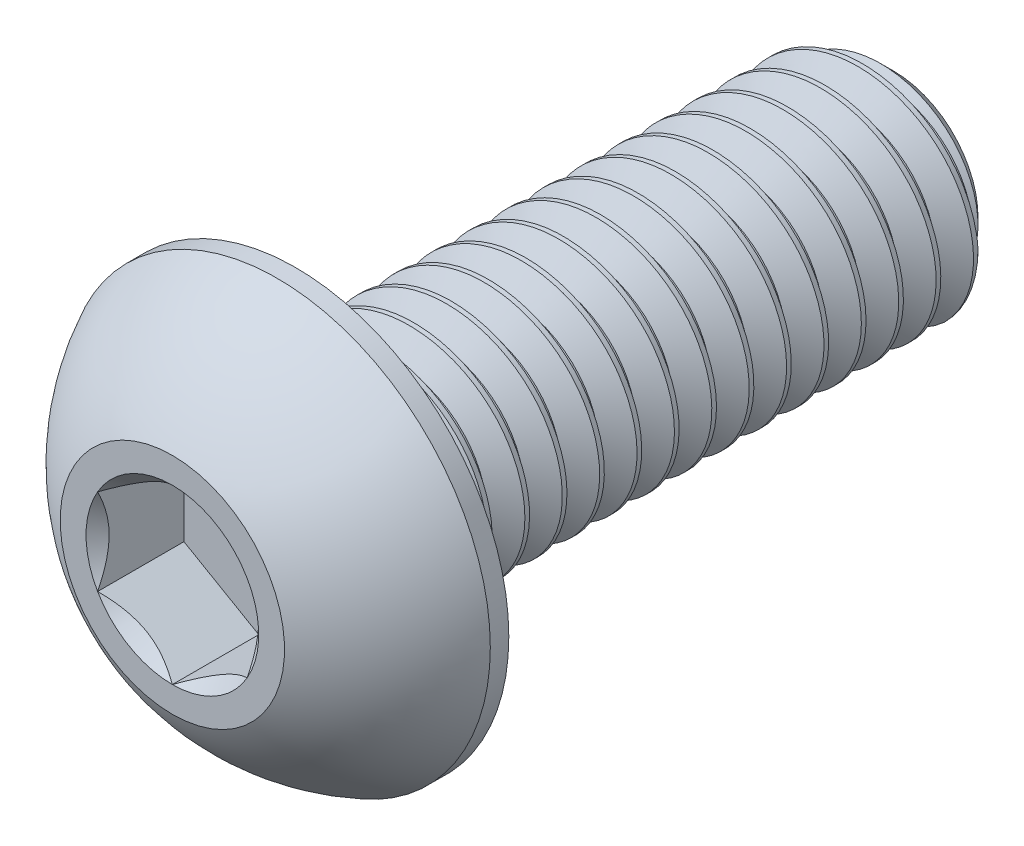
SolidWorks part; units mm, degrees
ref_plane "Front" through (0, 0, 0) normal (0, 0, 1) x (1, 0, 0)
ref_plane "Top" through (0, 0, 0) normal (0, 1, 0) x (1, 0, 0)
ref_plane "Right" through (0, 0, 0) normal (1, 0, 0) x (0, 0, -1)
sketch "Sketch1" plane through (0, 0, 0) normal (1, 0, 0) x (0, 0, -1)
  line L2 (1.65, 1.5) -> (9.65, 1.5)
  line L3 (9.65, 1.5) -> (9.65, 0)
  line L4 (9.65, 0) -> (1.65, 0)
  line L6 (1.4025, 2.85) -> (1.65, 2.85) construction
  line L7 (9.65, 1.5) -> (9.65, -1.5) construction
  line L8 (0, 0) -> (1.65, 0) construction
  line L9 (1.65, 2.85) -> (1.65, -2.85) construction
  line L11 (1.65, 1.5) -> (1.65, 0)
  line L13 (0, 1) -> (0, -1) construction
  line L14 (0, 1) -> (0, 1.5) construction
  arc A3 (0, 1.5) -> (1.4025, 2.85) centre (2.7948, 0) cw construction
  dimension "D1" = 0.2475
  dimension "Head Ht" = 1.65
  dimension "Head Dia" = 5.7
  dimension "Dia" = 3
  dimension "Lg" = 8
  dimension "Hex" = 2
revolve "Revolve1" add sketch "Sketch1" angle 360 mid plane about L4
sketch "Sketch3" plane through (0, 0, -9.65) normal (0, 0, -1) x (-1, 0, 0)
  circle A0 centre (0, 0) radius 1.5
curve "Helix/Spiral1" pitch 0.5 height 8.5 radius 1.5 centre (0, 0, -9.65) axis (0, 0, 1) start towards (0, 1, 0)
sketch "Sketch2" plane through (0, 0, 0) normal (1, 0, 0) x (0, 0, -1)
  line L0 (9.65, 1.5) -> (10.0875, 1.5)
  line L1 (10.0875, 1.5) -> (9.9, 1.1752)
  line L2 (9.9, 1.1752) -> (9.8375, 1.1752)
  line L3 (9.8375, 1.1752) -> (9.65, 1.5)
  line L4 (9.7438, 1.3376) -> (9.9938, 1.3376) construction
  dimension "D1" = 60
  dimension "D2" = 0.0625
  dimension "D3" = 0.25
chamfer "Chamfer1" distance 0.375 angle 45 1 edges at (0, 1.5, -9.65)
sweep "Cut-Sweep1" cut profiles "Sketch2" path "Helix/Spiral1"
sketch "Sketch7" plane through (0, 0, 0) normal (1, 0, 0) x (0, 0, -1)
  line L6 (1.4025, 2.85) -> (1.65, 2.85) construction
  line L8 (0, 0) -> (1.65, 0) construction
  line L11 (1.65, 2.85) -> (1.65, -2.85) construction
  line L12 (1.4025, 2.85) -> (1.65, 2.85)
  line L13 (0, 0) -> (1.65, 0)
  line L14 (0, 1) -> (0, -1) construction
  line L15 (1.65, 2.85) -> (1.65, 0)
  line L16 (0, 1.5) -> (0, 0)
  arc A2 (1.4025, 2.85) -> (0, 1.5) centre (2.7948, 0) ccw construction
  arc A3 (1.4025, 2.85) -> (0, 1.5) centre (2.7948, 0) ccw
revolve "Revolve2" add sketch "Sketch7" angle 360 mid plane about L13
sketch "Sketch5" plane through (0, 0, 0) normal (0, 0, 1) x (1, 0, 0)
  line L1 (1, -0.5774) -> (1, 0.5774)
  line L2 (1, 0.5774) -> (0, 1.1547)
  line L3 (0, 1.1547) -> (-1, 0.5774)
  line L4 (-1, 0.5774) -> (-1, -0.5774)
  line L5 (-1, -0.5774) -> (0, -1.1547)
  line L6 (0, -1.1547) -> (1, -0.5774)
  circle A0 centre (0, 0) radius 1 construction
extrude "Cut-Extrude2" cut sketch "Sketch5" against normal blind 1.155
sketch "Sketch6" plane through (0, 0, 0) normal (0, 0, 1) x (1, 0, 0)
  circle A0 centre (0, 0) radius 1.1547
extrude "Cut-Extrude3" cut sketch "Sketch6" against normal blind 1.155 draft 45
sketch "Sketch9" [suppressed] plane through (0, 0, -4.2164) normal (0, 0, 1) x (1, 0, 0)
  circle A2 centre (0, 0) radius 3.9687
extrude "Boss-Extrude2" [suppressed] add sketch "Sketch9" against normal offset from surface (9.525 mm away) 28.575 up to face at (0, 1.125, -9.65)
sketch "Sketch10" plane through (0, 0, 0) normal (1, 0, 0) x (0, 0, -1)
  line L0 (9.65, 1.5) -> (9.65, -1.5) construction
  point P0 (8.9, -1.5)
  dimension "D1" = 0.75
equation "\"D3@Helix/Spiral1\" = \"Lg@Sketch1\" + \"D4@Helix/Spiral1\""
equation "\"D2@Sketch2\" = \"D4@Helix/Spiral1\" * .125"
equation "\"D3@Sketch2\" = \"D4@Helix/Spiral1\" * .5"
equation "\"D1@Chamfer1\" = \"D4@Helix/Spiral1\" * .75"
equation "\"D1@Cut-Extrude2\" = \"Head Ht@Sketch1\" * .7"
equation "\"D1@Sketch1\" = \"Head Ht@Sketch1\" * .15"
equation "\"D1@Sketch10\" = \"D4@Helix/Spiral1\" * 1.5"
equation "\"D1@Cut-Extrude3\" = \"D1@Cut-Extrude2\""
